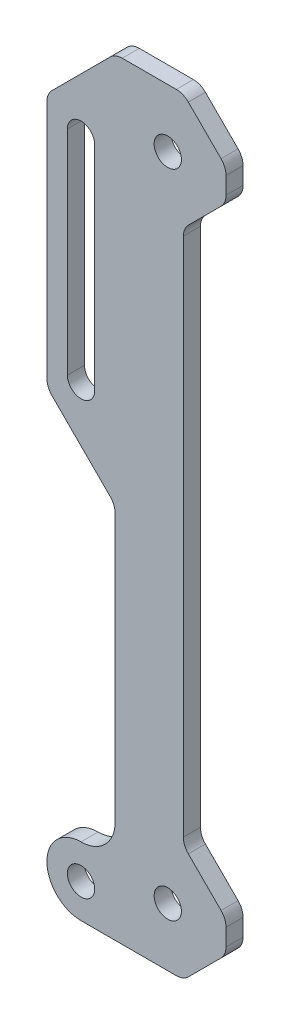
SolidWorks part; units mm, degrees
material "Thornel Mat VMA"
ref_plane "Front Plane" through (0, 0, 0) normal (0, 0, 1) x (1, 0, 0)
ref_plane "Top Plane" through (0, 0, 0) normal (0, 1, 0) x (1, 0, 0)
ref_plane "Right Plane" through (0, 0, 0) normal (1, 0, 0) x (0, 0, -1)
sketch "Sketch1" plane through (0, 0, 0) normal (0, 0, 1) x (1, 0, 0)
  line L2 (17.6, -85.4) -> (17.6, -60.4)
  line L3 (14.4, -60.4) -> (14.4, -85.4)
  line L4 (17.6, -85.4) -> (17.6, -60.4)
  line L5 (14.4, -60.4) -> (14.4, -85.4)
  line L19 (28, -126.3397) -> (28, -63.6603)
  line L20 (28, -63.6603) -> (33, -58.6603)
  line L21 (33, -58.6603) -> (33, -55)
  line L22 (33, -55) -> (28, -50)
  line L23 (28, -50) -> (20, -50)
  line L24 (20, -50) -> (12, -58)
  line L25 (12, -58) -> (12, -87.8)
  line L26 (12, -87.8) -> (20, -95.8)
  line L27 (20, -95.8) -> (20, -132)
  line L28 (20, -132) -> (12, -132)
  line L29 (12, -132) -> (12, -140)
  line L30 (12, -140) -> (28, -140)
  line L31 (28, -140) -> (33, -135)
  line L32 (33, -135) -> (33, -131.3397)
  line L33 (33, -131.3397) -> (28, -126.3397)
  line L34 (28, -126.3397) -> (28, -63.6603)
  line L35 (28, -63.6603) -> (33, -58.6603)
  line L36 (33, -58.6603) -> (33, -55)
  line L37 (33, -55) -> (28, -50)
  line L38 (28, -50) -> (20, -50)
  line L39 (20, -50) -> (12, -58)
  line L40 (12, -58) -> (12, -87.8)
  line L41 (12, -87.8) -> (20, -95.8)
  line L42 (20, -95.8) -> (20, -132)
  line L43 (20, -132) -> (12, -132)
  line L44 (12, -132) -> (12, -140)
  line L45 (12, -140) -> (28, -140)
  line L46 (28, -140) -> (33, -135)
  line L47 (33, -135) -> (33, -131.3397)
  line L48 (33, -131.3397) -> (28, -126.3397)
  circle A1 centre (26.1699, -133.1699) radius 1.6
  circle A2 centre (26.1699, -133.1699) radius 1.6
  circle A3 centre (26.1699, -56.8301) radius 1.6
  circle A4 centre (26.1699, -56.8301) radius 1.6
  circle A5 centre (16, -136) radius 1.6
  circle A6 centre (16, -136) radius 1.6
  arc A8 (14.4, -85.4) -> (17.6, -85.4) centre (16, -85.4) ccw
  arc A9 (17.6, -60.4) -> (14.4, -60.4) centre (16, -60.4) ccw
  arc A10 (14.4, -85.4) -> (17.6, -85.4) centre (16, -85.4) ccw
  arc A11 (17.6, -60.4) -> (14.4, -60.4) centre (16, -60.4) ccw
  dimension "D1" = 0
  dimension "D2" = 0
  dimension "D3" = 0
  dimension "D4" = 0
  dimension "D5" = 0
extrude "Boss-Extrude1" add sketch "Sketch1" along normal blind 2
fillet "Fillet1" radius 4 3 edges at (12, -140, 1) (20, -132, 1) (12, -132, 1)
fillet "Fillet2" radius 2 12 edges at (12, -87.8, 1) (12, -58, 1) (20, -50, 1) (28, -50, 1) (33, -55, 1) (33, -58.6603, 1) (28, -63.6603, 1) (28, -126.3397, 1) (33, -131.3397, 1) (33, -135, 1) (28, -140, 1) (20, -95.8, 1)
